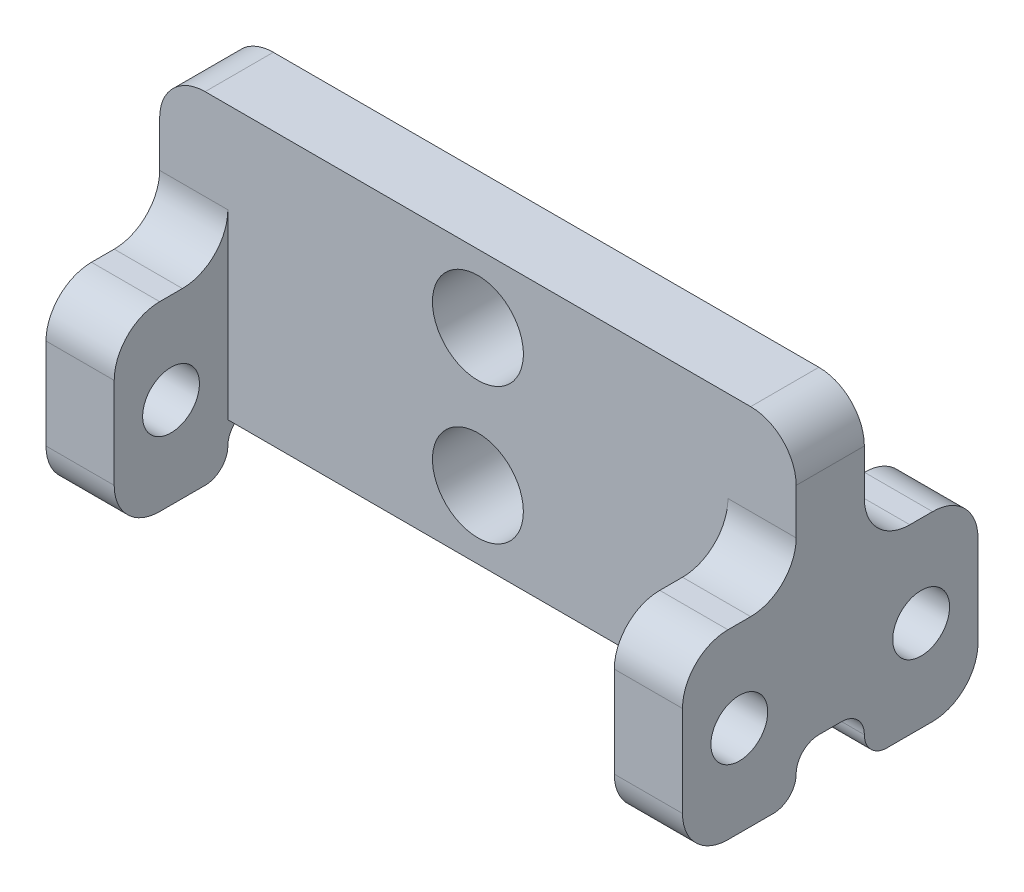
SolidWorks part; units mm, degrees
material "ABS"
ref_plane "前视基准面" through (0, 0, 0) normal (0, 0, 1) x (1, 0, 0)
ref_plane "上视基准面" through (0, 0, 0) normal (0, 1, 0) x (1, 0, 0)
ref_plane "右视基准面" through (0, 0, 0) normal (1, 0, 0) x (0, 0, -1)
sketch "草图1" plane through (0, 0, 0) normal (0, 0, 1) x (1, 0, 0)
  line L0 (0, 0) -> (0, 12) construction
  line L1 (14, 0) -> (-14, 0)
  line L2 (-14, 0) -> (-14, 12)
  line L3 (-14, 12) -> (14, 12)
  line L4 (-3.9373, 6) -> (3.5244, 6) construction
  line L5 (14, 0) -> (14, 12)
  circle A0 centre (0, 3) radius 2
  circle A1 centre (0, 9) radius 2
  dimension "D2" = 14
  dimension "D4" = 3
  dimension "D3" = 4
  dimension "D1" = 12
extrude "凸台-拉伸1" add sketch "草图1" along normal mid plane 3
sketch "草图2" plane through (-14, 0, 0) normal (-1, 0, 0) x (0, 0, 1)
  line L0 (0, 4) -> (0, -1.4762) construction
  line L1 (1.5, 6) -> (6.5, 6)
  line L2 (1.5, 6) -> (1.5, -2)
  line L3 (1.5, -2) -> (6.5, -2)
  line L4 (6.5, 6) -> (6.5, -2)
  line L5 (1.5, 12) -> (1.5, 0) construction
  line L7 (-6.5, 6) -> (-6.5, -2)
  line L8 (-1.5, -2) -> (-6.5, -2)
  line L9 (-1.5, 6) -> (-1.5, -2)
  line L10 (-1.5, 6) -> (-6.5, 6)
  line L11 (1.5, 12) -> (-1.5, 12) construction
  dimension "D1" = 8
  dimension "D2" = 5
  dimension "D3" = 6
extrude "凸台-拉伸2" add sketch "草图2" against normal blind 3
sketch "草图4" plane through (-14, 0, 0) normal (-1, 0, 0) x (0, 0, 1)
  line L0 (0, 3.7174) -> (0, -2.5851) construction
  line L3 (1.5, -2) -> (6.5, -2) construction
  circle A0 centre (4, 2) radius 1.25
  circle A1 centre (-4, 2) radius 1.25
  dimension "D1" = 2.5
  dimension "D2" = 4
  dimension "D3" = 4
extrude "切除-拉伸2" cut sketch "草图4" against normal blind 5
mirror "镜向1" about plane through (0, 0, 0) normal (1, 0, 0) of "切除-拉伸2", "凸台-拉伸2"
fillet "圆角1" radius 2 14 edges at (12.5, -2, 6.5) (12.5, 6, 6.5) (-12.5, -2, 6.5) (-12.5, 6, 6.5) (-12.5, 6, 1.5) (-12.5, 6, -1.5) (-12.5, 6, -6.5) (12.5, 6, -1.5) (12.5, 6, -6.5) (12.5, -2, -6.5) (-12.5, -2, -6.5) (14, 12, 0) (-14, 12, 0) (12.5, 6, 1.5)
fillet "圆角2" radius 1 8 edges at (12.5, -2, -1.5) (12.5, 0, -1.5) (12.5, -2, 1.5) (12.5, 0, 1.5) (-12.5, -2, 1.5) (-12.5, 0, 1.5) (-12.5, -2, -1.5) (-12.5, 0, -1.5)
